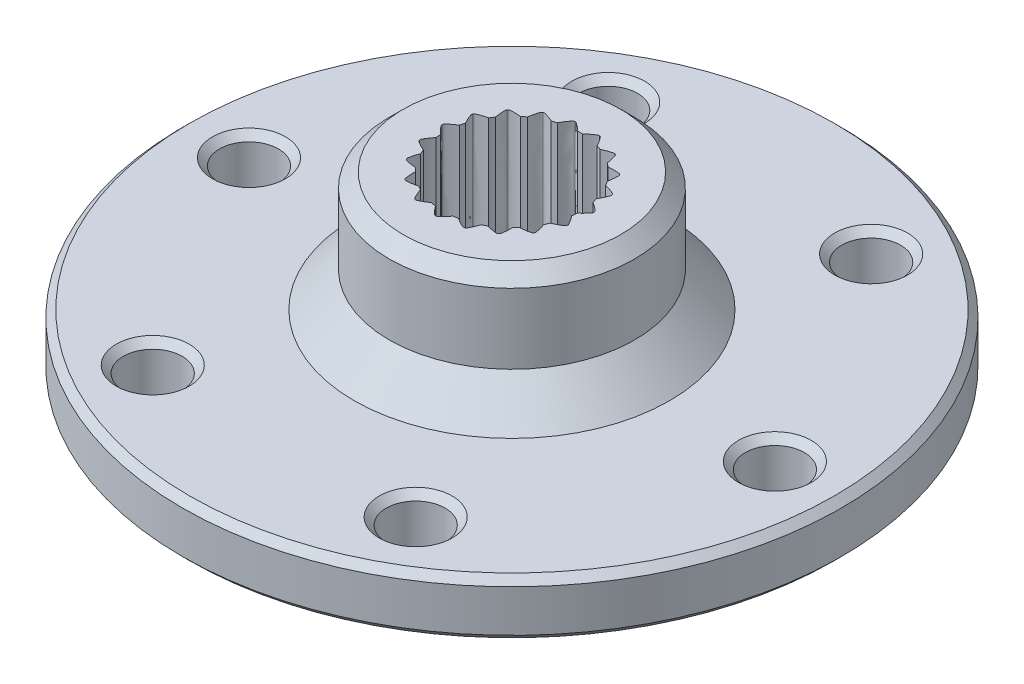
SolidWorks part; units mm, degrees
material "AISI 4340 Steel, normalized"
ref_plane "Front Plane" through (0, 0, 0) normal (0, 0, 1) x (1, 0, 0)
ref_plane "Top Plane" through (0, 0, 0) normal (0, 1, 0) x (1, 0, 0)
ref_plane "Right Plane" through (0, 0, 0) normal (1, 0, 0) x (0, 0, -1)
sketch "Sketch1" plane through (0, 0, 0) normal (0, 1, 0) x (1, 0, 0)
  circle A8 centre (0, 0) radius 47
  circle A9 centre (0, 0) radius 28
  circle A11 centre (-18.75, -32.476) radius 4.55
  circle A12 centre (18.75, -32.476) radius 4.55
  circle A13 centre (37.5, 0) radius 4.55
  circle A14 centre (18.75, 32.476) radius 4.55
  circle A15 centre (-18.75, 32.476) radius 4.55
  circle A16 centre (-37.5, 0) radius 4.55
  circle A17 centre (0, 0) radius 37.5 construction
  dimension "D1" = 94
  dimension "D2" = 56
  dimension "D3" = 9.1
  dimension "D5" = 75
  dimension "D4" = 18.75
extrude "Boss-Extrude1" add sketch "Sketch1" along normal blind 8 contours A9 | A8 A16 A15 A14 A13 A12 A11 A9 | A15 | A14 | A13 | A12 | A11 | A16 region at (-45.6706, 0, 0) region at (0, 0, 0) region at (-18.75, 0, 32.476) region at (18.75, 0, 32.476) region at (37.5, 0, 0) region at (18.75, 0, -32.476) region at (-18.75, 0, -32.476)
sketch "Sketch17" plane through (0, 8, 0) normal (0, 1, 0) x (1, 0, 0)
  circle A0 centre (-18.75, -32.476) radius 4.55
  circle A1 centre (18.75, -32.476) radius 4.55
  circle A2 centre (37.5, 0) radius 4.55
  circle A3 centre (18.75, 32.476) radius 4.55
  circle A4 centre (-18.75, 32.476) radius 4.55
  circle A5 centre (-37.5, 0) radius 4.55
  circle A6 centre (0, 0) radius 37.5 construction
  circle A7 centre (0, 0) radius 47 construction
  point P1 (-37.5, 0)
  point P2 (-18.75, -32.476)
  point P3 (18.75, -32.476)
  point P4 (37.5, 0)
  point P5 (18.75, 32.476)
  point P6 (-18.75, 32.476)
  dimension "D1" = 9.1
  dimension "D2" = 75
  dimension "D3" = 18.75
  dimension "D4" = 37.5
hole_wizard "M8 Clearance Hole1" positions "Sketch17" profile "Sketch18" hole size "M8" standard "DIN" end condition through all
sketch "Sketch18" plane through (-18.75, 8, -32.476) normal (1, 0, 0) x (0, 0, 1)
  line L0 (0, 0) -> (0, 8)
  line L1 (0, 8) -> (4.2, 8)
  line L2 (4.2, 8) -> (4.2, 0)
  line L5 (4.2, 0) -> (0, 0)
  line L11 (0, -6.35) -> (0, 107.95) construction
  dimension "Thru Hole Dia." = 8.4
  dimension "Thru Hole Depth" = 8
sketch "Sketch12" plane through (0, 8, 0) normal (0, 1, 0) x (1, 0, 0)
  circle A0 centre (0, 0) radius 17.5
  dimension "D1" = 35
extrude "Boss-Extrude5" add sketch "Sketch12" along normal blind 17 contours A0
sketch "Sketch13" plane through (0, 0, 0) normal (0, -1, 0) x (1, 0, 0)
  circle A0 centre (0, 0) radius 28
  dimension "D1" = 56
extrude "Boss-Extrude6" add sketch "Sketch13" along normal blind 5.08
sketch "Sketch16" plane through (0, 0, 0) normal (0, 1, 0) x (1, 0, 0)
  line B0 (1.8668, 11.187) -> (2.1421, 11.1376)
  line B1 (2.1421, 11.1376) -> (2.416, 11.0814)
  line B2 (2.416, 11.0814) -> (2.491, 11.1676)
  line B3 (2.491, 11.1676) -> (2.5708, 11.2556)
  line B4 (2.5708, 11.2556) -> (2.6534, 11.343)
  line B5 (2.6534, 11.343) -> (2.7388, 11.4297)
  line B6 (2.7388, 11.4297) -> (2.8266, 11.5155)
  line B7 (2.8266, 11.5155) -> (2.9189, 11.6021)
  line B8 (2.9189, 11.6021) -> (3.0133, 11.6874)
  line B9 (3.0133, 11.6874) -> (3.1122, 11.7733)
  line B10 (3.1122, 11.7733) -> (3.2129, 11.8575)
  line B11 (3.2129, 11.8575) -> (3.3178, 11.942)
  line B12 (3.3178, 11.942) -> (3.4243, 12.0245)
  line B13 (3.4243, 12.0245) -> (3.5292, 12.1028)
  line B14 (3.5292, 12.1028) -> (3.5601, 12.1214)
  line B15 (3.5601, 12.1214) -> (3.594, 12.1339)
  line B16 (3.594, 12.1339) -> (3.6296, 12.14)
  line B17 (3.6296, 12.14) -> (3.6657, 12.1394)
  line B18 (3.6657, 12.1394) -> (3.701, 12.1321)
  line B19 (3.701, 12.1321) -> (3.9104, 12.0662)
  line B20 (3.9104, 12.0662) -> (4.1185, 11.9968)
  line B21 (4.1185, 11.9968) -> (4.3254, 11.9237)
  line B22 (4.3254, 11.9237) -> (4.531, 11.8471)
  line B23 (4.531, 11.8471) -> (4.5634, 11.8312)
  line B24 (4.5634, 11.8312) -> (4.5923, 11.8095)
  line B25 (4.5923, 11.8095) -> (4.6167, 11.7829)
  line B26 (4.6167, 11.7829) -> (4.6357, 11.7522)
  line B27 (4.6357, 11.7522) -> (4.6487, 11.7185)
  line B28 (4.6487, 11.7185) -> (4.6833, 11.5923)
  line B29 (4.6833, 11.5923) -> (4.7167, 11.4617)
  line B30 (4.7167, 11.4617) -> (4.7476, 11.3306)
  line B31 (4.7476, 11.3306) -> (4.7754, 11.2023)
  line B32 (4.7754, 11.2023) -> (4.8006, 11.0738)
  line B33 (4.8006, 11.0738) -> (4.8228, 10.9485)
  line B34 (4.8228, 10.9485) -> (4.8424, 10.8235)
  line B35 (4.8424, 10.8235) -> (4.859, 10.7019)
  line B36 (4.859, 10.7019) -> (4.8731, 10.581)
  line B37 (4.8731, 10.581) -> (4.8846, 10.4612)
  line B38 (4.8846, 10.4612) -> (4.8935, 10.3428)
  line B39 (4.8935, 10.3428) -> (4.8997, 10.2287)
  line B40 (4.8997, 10.2287) -> (5.1505, 10.1048)
  line B41 (5.1505, 10.1048) -> (5.398, 9.9747)
  line B42 (5.398, 9.9747) -> (5.6424, 9.8386)
  line B43 (5.6424, 9.8386) -> (5.8832, 9.6965)
  line B44 (5.8832, 9.6965) -> (5.9822, 9.7537)
  line B45 (5.9822, 9.7537) -> (6.0861, 9.811)
  line B46 (6.0861, 9.811) -> (6.1927, 9.8669)
  line B47 (6.1927, 9.8669) -> (6.3016, 9.9212)
  line B48 (6.3016, 9.9212) -> (6.4125, 9.9737)
  line B49 (6.4125, 9.9737) -> (6.5279, 10.0257)
  line B50 (6.5279, 10.0257) -> (6.645, 10.0757)
  line B51 (6.645, 10.0757) -> (6.7663, 10.1248)
  line B52 (6.7663, 10.1248) -> (6.8889, 10.1718)
  line B53 (6.8889, 10.1718) -> (7.0156, 10.2176)
  line B54 (7.0156, 10.2176) -> (7.1431, 10.2611)
  line B55 (7.1431, 10.2611) -> (7.2677, 10.3012)
  line B56 (7.2677, 10.3012) -> (7.303, 10.3087)
  line B57 (7.303, 10.3087) -> (7.3391, 10.3095)
  line B58 (7.3391, 10.3095) -> (7.3748, 10.3037)
  line B59 (7.3748, 10.3037) -> (7.4087, 10.2914)
  line B60 (7.4087, 10.2914) -> (7.4398, 10.273)
  line B61 (7.4398, 10.273) -> (7.6164, 10.1428)
  line B62 (7.6164, 10.1428) -> (7.7907, 10.0095)
  line B63 (7.7907, 10.0095) -> (7.9627, 9.8732)
  line B64 (7.9627, 9.8732) -> (8.1323, 9.734)
  line B65 (8.1323, 9.734) -> (8.1577, 9.7084)
  line B66 (8.1577, 9.7084) -> (8.178, 9.6785)
  line B67 (8.178, 9.6785) -> (8.1924, 9.6454)
  line B68 (8.1924, 9.6454) -> (8.2004, 9.6102)
  line B69 (8.2004, 9.6102) -> (8.2018, 9.5741)
  line B70 (8.2018, 9.5741) -> (8.1936, 9.4435)
  line B71 (8.1936, 9.4435) -> (8.1827, 9.3092)
  line B72 (8.1827, 9.3092) -> (8.1694, 9.1751)
  line B73 (8.1694, 9.1751) -> (8.154, 9.0448)
  line B74 (8.154, 9.0448) -> (8.1362, 8.9151)
  line B75 (8.1362, 8.9151) -> (8.1164, 8.7894)
  line B76 (8.1164, 8.7894) -> (8.0944, 8.6647)
  line B77 (8.0944, 8.6647) -> (8.0706, 8.5443)
  line B78 (8.0706, 8.5443) -> (8.0447, 8.4254)
  line B79 (8.0447, 8.4254) -> (8.0167, 8.3084)
  line B80 (8.0167, 8.3084) -> (7.9867, 8.1935)
  line B81 (7.9867, 8.1935) -> (7.9555, 8.0835)
  line B82 (7.9555, 8.0835) -> (8.1524, 7.8849)
  line B83 (8.1524, 7.8849) -> (8.3443, 7.6815)
  line B84 (8.3443, 7.6815) -> (8.5312, 7.4734)
  line B85 (8.5312, 7.4734) -> (8.7129, 7.2608)
  line B86 (8.7129, 7.2608) -> (8.8251, 7.2828)
  line B87 (8.8251, 7.2828) -> (8.942, 7.3032)
  line B88 (8.942, 7.3032) -> (9.061, 7.3215)
  line B89 (9.061, 7.3215) -> (9.1816, 7.3375)
  line B90 (9.1816, 7.3375) -> (9.3035, 7.3512)
  line B91 (9.3035, 7.3512) -> (9.4296, 7.3629)
  line B92 (9.4296, 7.3629) -> (9.5565, 7.3722)
  line B93 (9.5565, 7.3722) -> (9.6872, 7.3792)
  line B94 (9.6872, 7.3792) -> (9.8184, 7.3838)
  line B95 (9.8184, 7.3838) -> (9.9531, 7.386)
  line B96 (9.9531, 7.386) -> (10.0879, 7.3858)
  line B97 (10.0879, 7.3858) -> (10.2187, 7.3832)
  line B98 (10.2187, 7.3832) -> (10.2546, 7.3788)
  line B99 (10.2546, 7.3788) -> (10.289, 7.3679)
  line B100 (10.289, 7.3679) -> (10.3208, 7.3508)
  line B101 (10.3208, 7.3508) -> (10.3489, 7.3282)
  line B102 (10.3489, 7.3282) -> (10.3723, 7.3007)
  line B103 (10.3723, 7.3007) -> (10.4971, 7.1202)
  line B104 (10.4971, 7.1202) -> (10.6187, 6.9375)
  line B105 (10.6187, 6.9375) -> (10.7371, 6.7528)
  line B106 (10.7371, 6.7528) -> (10.8523, 6.566)
  line B107 (10.8523, 6.566) -> (10.868, 6.5336)
  line B108 (10.868, 6.5336) -> (10.8775, 6.4987)
  line B109 (10.8775, 6.4987) -> (10.8804, 6.4627)
  line B110 (10.8804, 6.4627) -> (10.8765, 6.4268)
  line B111 (10.8765, 6.4268) -> (10.8661, 6.3922)
  line B112 (10.8661, 6.3922) -> (10.8159, 6.2714)
  line B113 (10.8159, 6.2714) -> (10.7621, 6.1479)
  line B114 (10.7621, 6.1479) -> (10.7059, 6.0254)
  line B115 (10.7059, 6.0254) -> (10.649, 5.9071)
  line B116 (10.649, 5.9071) -> (10.59, 5.7902)
  line B117 (10.59, 5.7902) -> (10.5305, 5.6777)
  line B118 (10.5305, 5.6777) -> (10.4692, 5.567)
  line B119 (10.4692, 5.567) -> (10.4077, 5.4608)
  line B120 (10.4077, 5.4608) -> (10.3446, 5.3568)
  line B121 (10.3446, 5.3568) -> (10.2801, 5.2552)
  line B122 (10.2801, 5.2552) -> (10.2144, 5.1563)
  line B123 (10.2144, 5.1563) -> (10.1492, 5.0624)
  line B124 (10.1492, 5.0624) -> (10.2709, 4.8106)
  line B125 (10.2709, 4.8106) -> (10.3864, 4.5559)
  line B126 (10.3864, 4.5559) -> (10.4956, 4.2984)
  line B127 (10.4956, 4.2984) -> (10.5984, 4.0383)
  line B128 (10.5984, 4.0383) -> (10.7116, 4.0227)
  line B129 (10.7116, 4.0227) -> (10.8289, 4.0041)
  line B130 (10.8289, 4.0041) -> (10.9473, 3.9827)
  line B131 (10.9473, 3.9827) -> (11.0666, 3.9587)
  line B132 (11.0666, 3.9587) -> (11.1864, 3.932)
  line B133 (11.1864, 3.932) -> (11.3094, 3.9022)
  line B134 (11.3094, 3.9022) -> (11.4324, 3.8697)
  line B135 (11.4324, 3.8697) -> (11.5584, 3.834)
  line B136 (11.5584, 3.834) -> (11.684, 3.7957)
  line B137 (11.684, 3.7957) -> (11.8121, 3.7541)
  line B138 (11.8121, 3.7541) -> (11.9394, 3.7101)
  line B139 (11.9394, 3.7101) -> (12.0624, 3.6651)
  line B140 (12.0624, 3.6651) -> (12.0948, 3.6494)
  line B141 (12.0948, 3.6494) -> (12.1238, 3.6279)
  line B142 (12.1238, 3.6279) -> (12.1484, 3.6014)
  line B143 (12.1484, 3.6014) -> (12.1676, 3.5708)
  line B144 (12.1676, 3.5708) -> (12.1808, 3.5372)
  line B145 (12.1808, 3.5372) -> (12.2402, 3.326)
  line B146 (12.2402, 3.326) -> (12.2959, 3.1137)
  line B147 (12.2959, 3.1137) -> (12.3479, 2.9006)
  line B148 (12.3479, 2.9006) -> (12.3963, 2.6865)
  line B149 (12.3963, 2.6865) -> (12.4006, 2.6507)
  line B150 (12.4006, 2.6507) -> (12.3983, 2.6147)
  line B151 (12.3983, 2.6147) -> (12.3893, 2.5797)
  line B152 (12.3893, 2.5797) -> (12.374, 2.547)
  line B153 (12.374, 2.547) -> (12.3529, 2.5177)
  line B154 (12.3529, 2.5177) -> (12.2662, 2.4196)
  line B155 (12.2662, 2.4196) -> (12.1752, 2.3203)
  line B156 (12.1752, 2.3203) -> (12.0823, 2.2227)
  line B157 (12.0823, 2.2227) -> (11.9901, 2.1293)
  line B158 (11.9901, 2.1293) -> (11.8963, 2.0379)
  line B159 (11.8963, 2.0379) -> (11.8035, 1.9508)
  line B160 (11.8035, 1.9508) -> (11.7096, 1.866)
  line B161 (11.7096, 1.866) -> (11.6169, 1.7856)
  line B162 (11.6169, 1.7856) -> (11.5234, 1.7077)
  line B163 (11.5234, 1.7077) -> (11.4294, 1.6325)
  line B164 (11.4294, 1.6325) -> (11.3352, 1.5603)
  line B165 (11.3352, 1.5603) -> (11.243, 1.4927)
  line B166 (11.243, 1.4927) -> (11.2764, 1.215)
  line B167 (11.2764, 1.215) -> (11.3029, 0.9366)
  line B168 (11.3029, 0.9366) -> (11.3226, 0.6576)
  line B169 (11.3226, 0.6576) -> (11.3354, 0.3782)
  line B170 (11.3354, 0.3782) -> (11.4374, 0.3267)
  line B171 (11.4374, 0.3267) -> (11.5422, 0.271)
  line B172 (11.5422, 0.271) -> (11.6473, 0.2123)
  line B173 (11.6473, 0.2123) -> (11.7523, 0.1509)
  line B174 (11.7523, 0.1509) -> (11.857, 0.0868)
  line B175 (11.857, 0.0868) -> (11.9636, 0.0186)
  line B176 (11.9636, 0.0186) -> (12.0695, -0.0521)
  line B177 (12.0695, -0.0521) -> (12.177, -0.1268)
  line B178 (12.177, -0.1268) -> (12.2834, -0.2037)
  line B179 (12.2834, -0.2037) -> (12.391, -0.2847)
  line B180 (12.391, -0.2847) -> (12.4972, -0.3677)
  line B181 (12.4972, -0.3677) -> (12.5988, -0.4501)
  line B182 (12.5988, -0.4501) -> (12.6245, -0.4756)
  line B183 (12.6245, -0.4756) -> (12.6449, -0.5053)
  line B184 (12.6449, -0.5053) -> (12.6595, -0.5383)
  line B185 (12.6595, -0.5383) -> (12.6678, -0.5735)
  line B186 (12.6678, -0.5735) -> (12.6694, -0.6096)
  line B187 (12.6694, -0.6096) -> (12.6569, -0.8286)
  line B188 (12.6569, -0.8286) -> (12.6407, -1.0474)
  line B189 (12.6407, -1.0474) -> (12.6207, -1.2659)
  line B190 (12.6207, -1.2659) -> (12.5969, -1.4841)
  line B191 (12.5969, -1.4841) -> (12.5894, -1.5194)
  line B192 (12.5894, -1.5194) -> (12.5755, -1.5527)
  line B193 (12.5755, -1.5527) -> (12.5556, -1.5829)
  line B194 (12.5556, -1.5829) -> (12.5305, -1.6088)
  line B195 (12.5305, -1.6088) -> (12.5011, -1.6297)
  line B196 (12.5011, -1.6297) -> (12.3872, -1.6943)
  line B197 (12.3872, -1.6943) -> (12.2689, -1.7587)
  line B198 (12.2689, -1.7587) -> (12.1494, -1.8208)
  line B199 (12.1494, -1.8208) -> (12.0318, -1.8792)
  line B200 (12.0318, -1.8792) -> (11.9135, -1.9352)
  line B201 (11.9135, -1.9352) -> (11.7974, -1.9875)
  line B202 (11.7974, -1.9875) -> (11.681, -2.0372)
  line B203 (11.681, -2.0372) -> (11.5672, -2.0832)
  line B204 (11.5672, -2.0832) -> (11.4535, -2.1265)
  line B205 (11.4535, -2.1265) -> (11.3402, -2.1671)
  line B206 (11.3402, -2.1671) -> (11.2277, -2.2048)
  line B207 (11.2277, -2.2048) -> (11.1185, -2.2388)
  line B208 (11.1185, -2.2388) -> (11.0599, -2.5123)
  line B209 (11.0599, -2.5123) -> (10.9946, -2.7842)
  line B210 (10.9946, -2.7842) -> (10.9226, -3.0545)
  line B211 (10.9226, -3.0545) -> (10.844, -3.3229)
  line B212 (10.844, -3.3229) -> (10.9238, -3.4047)
  line B213 (10.9238, -3.4047) -> (11.0048, -3.4915)
  line B214 (11.0048, -3.4915) -> (11.0852, -3.5811)
  line B215 (11.0852, -3.5811) -> (11.1645, -3.6733)
  line B216 (11.1645, -3.6733) -> (11.2427, -3.7679)
  line B217 (11.2427, -3.7679) -> (11.3214, -3.867)
  line B218 (11.3214, -3.867) -> (11.3986, -3.9682)
  line B219 (11.3986, -3.9682) -> (11.4761, -4.0738)
  line B220 (11.4761, -4.0738) -> (11.5517, -4.1811)
  line B221 (11.5517, -4.1811) -> (11.6272, -4.2927)
  line B222 (11.6272, -4.2927) -> (11.7007, -4.4056)
  line B223 (11.7007, -4.4056) -> (11.7701, -4.5165)
  line B224 (11.7701, -4.5165) -> (11.786, -4.5489)
  line B225 (11.786, -4.5489) -> (11.7957, -4.5837)
  line B226 (11.7957, -4.5837) -> (11.7988, -4.6197)
  line B227 (11.7988, -4.6197) -> (11.7952, -4.6556)
  line B228 (11.7952, -4.6556) -> (11.785, -4.6903)
  line B229 (11.785, -4.6903) -> (11.7021, -4.8934)
  line B230 (11.7021, -4.8934) -> (11.6157, -5.0951)
  line B231 (11.6157, -5.0951) -> (11.5258, -5.2953)
  line B232 (11.5258, -5.2953) -> (11.4325, -5.4939)
  line B233 (11.4325, -5.4939) -> (11.4139, -5.5248)
  line B234 (11.4139, -5.5248) -> (11.3899, -5.5518)
  line B235 (11.3899, -5.5518) -> (11.3614, -5.5739)
  line B236 (11.3614, -5.5739) -> (11.3292, -5.5903)
  line B237 (11.3292, -5.5903) -> (11.2946, -5.6005)
  line B238 (11.2946, -5.6005) -> (11.1659, -5.6246)
  line B239 (11.1659, -5.6246) -> (11.0331, -5.6471)
  line B240 (11.0331, -5.6471) -> (10.8998, -5.6671)
  line B241 (10.8998, -5.6671) -> (10.7697, -5.6841)
  line B242 (10.7697, -5.6841) -> (10.6396, -5.6987)
  line B243 (10.6396, -5.6987) -> (10.5129, -5.7104)
  line B244 (10.5129, -5.7104) -> (10.3866, -5.7196)
  line B245 (10.3866, -5.7196) -> (10.2641, -5.7262)
  line B246 (10.2641, -5.7262) -> (10.1425, -5.7302)
  line B247 (10.1425, -5.7302) -> (10.0221, -5.7318)
  line B248 (10.0221, -5.7318) -> (9.9034, -5.7309)
  line B249 (9.9034, -5.7309) -> (9.7892, -5.7277)
  line B250 (9.7892, -5.7277) -> (9.6449, -5.9673)
  line B251 (9.6449, -5.9673) -> (9.4949, -6.2033)
  line B252 (9.4949, -6.2033) -> (9.339, -6.4355)
  line B253 (9.339, -6.4355) -> (9.1775, -6.6639)
  line B254 (9.1775, -6.6639) -> (9.2264, -6.7672)
  line B255 (9.2264, -6.7672) -> (9.2749, -6.8755)
  line B256 (9.2749, -6.8755) -> (9.3218, -6.9864)
  line B257 (9.3218, -6.9864) -> (9.3669, -7.0994)
  line B258 (9.3669, -7.0994) -> (9.4101, -7.2142)
  line B259 (9.4101, -7.2142) -> (9.4524, -7.3336)
  line B260 (9.4524, -7.3336) -> (9.4926, -7.4543)
  line B261 (9.4926, -7.4543) -> (9.5315, -7.5793)
  line B262 (9.5315, -7.5793) -> (9.5682, -7.7054)
  line B263 (9.5682, -7.7054) -> (9.6034, -7.8354)
  line B264 (9.6034, -7.8354) -> (9.6362, -7.9661)
  line B265 (9.6362, -7.9661) -> (9.6658, -8.0936)
  line B266 (9.6658, -8.0936) -> (9.6704, -8.1294)
  line B267 (9.6704, -8.1294) -> (9.6682, -8.1654)
  line B268 (9.6682, -8.1654) -> (9.6595, -8.2005)
  line B269 (9.6595, -8.2005) -> (9.6444, -8.2333)
  line B270 (9.6444, -8.2333) -> (9.6235, -8.2627)
  line B271 (9.6235, -8.2627) -> (9.4792, -8.428)
  line B272 (9.4792, -8.428) -> (9.332, -8.5907)
  line B273 (9.332, -8.5907) -> (9.182, -8.7508)
  line B274 (9.182, -8.7508) -> (9.0292, -8.9083)
  line B275 (9.0292, -8.9083) -> (9.0016, -8.9316)
  line B276 (9.0016, -8.9316) -> (8.9701, -8.9493)
  line B277 (8.9701, -8.9493) -> (8.9359, -8.9609)
  line B278 (8.9359, -8.9609) -> (8.9002, -8.966)
  line B279 (8.9002, -8.966) -> (8.8641, -8.9644)
  line B280 (8.8641, -8.9644) -> (8.7346, -8.9454)
  line B281 (8.7346, -8.9454) -> (8.6017, -8.9235)
  line B282 (8.6017, -8.9235) -> (8.4692, -8.8992)
  line B283 (8.4692, -8.8992) -> (8.3405, -8.8731)
  line B284 (8.3405, -8.8731) -> (8.2127, -8.8446)
  line B285 (8.2127, -8.8446) -> (8.0891, -8.8145)
  line B286 (8.0891, -8.8145) -> (7.9667, -8.7822)
  line B287 (7.9667, -8.7822) -> (7.8486, -8.7486)
  line B288 (7.8486, -8.7486) -> (7.7323, -8.713)
  line B289 (7.7323, -8.713) -> (7.618, -8.6754)
  line B290 (7.618, -8.6754) -> (7.506, -8.6361)
  line B291 (7.506, -8.6361) -> (7.399, -8.5959)
  line B292 (7.399, -8.5959) -> (7.1848, -8.7757)
  line B293 (7.1848, -8.7757) -> (6.9662, -8.9502)
  line B294 (6.9662, -8.9502) -> (6.7434, -9.1192)
  line B295 (6.7434, -9.1192) -> (6.5165, -9.2827)
  line B296 (6.5165, -9.2827) -> (6.5292, -9.3963)
  line B297 (6.5292, -9.3963) -> (6.5399, -9.5146)
  line B298 (6.5399, -9.5146) -> (6.5482, -9.6346)
  line B299 (6.5482, -9.6346) -> (6.5542, -9.7561)
  line B300 (6.5542, -9.7561) -> (6.5578, -9.8788)
  line B301 (6.5578, -9.8788) -> (6.559, -10.0054)
  line B302 (6.559, -10.0054) -> (6.5578, -10.1327)
  line B303 (6.5578, -10.1327) -> (6.5541, -10.2635)
  line B304 (6.5541, -10.2635) -> (6.5478, -10.3946)
  line B305 (6.5478, -10.3946) -> (6.5389, -10.5291)
  line B306 (6.5389, -10.5291) -> (6.5275, -10.6633)
  line B307 (6.5275, -10.6633) -> (6.5141, -10.7935)
  line B308 (6.5141, -10.7935) -> (6.5068, -10.8289)
  line B309 (6.5068, -10.8289) -> (6.4931, -10.8623)
  line B310 (6.4931, -10.8623) -> (6.4734, -10.8926)
  line B311 (6.4734, -10.8926) -> (6.4485, -10.9187)
  line B312 (6.4485, -10.9187) -> (6.4192, -10.9398)
  line B313 (6.4192, -10.9398) -> (6.229, -11.0492)
  line B314 (6.229, -11.0492) -> (6.0369, -11.1553)
  line B315 (6.0369, -11.1553) -> (5.8431, -11.258)
  line B316 (5.8431, -11.258) -> (5.6474, -11.3574)
  line B317 (5.6474, -11.3574) -> (5.6138, -11.3704)
  line B318 (5.6138, -11.3704) -> (5.5783, -11.377)
  line B319 (5.5783, -11.377) -> (5.5421, -11.3769)
  line B320 (5.5421, -11.3769) -> (5.5067, -11.3701)
  line B321 (5.5067, -11.3701) -> (5.4731, -11.3569)
  line B322 (5.4731, -11.3569) -> (5.3568, -11.2969)
  line B323 (5.3568, -11.2969) -> (5.2382, -11.233)
  line B324 (5.2382, -11.233) -> (5.1207, -11.1669)
  line B325 (5.1207, -11.1669) -> (5.0075, -11.1005)
  line B326 (5.0075, -11.1005) -> (4.8959, -11.032)
  line B327 (4.8959, -11.032) -> (4.7887, -10.9634)
  line B328 (4.7887, -10.9634) -> (4.6834, -10.8932)
  line B329 (4.6834, -10.8932) -> (4.5827, -10.8231)
  line B330 (4.5827, -10.8231) -> (4.4842, -10.7516)
  line B331 (4.4842, -10.7516) -> (4.3883, -10.6789)
  line B332 (4.3883, -10.6789) -> (4.2952, -10.6053)
  line B333 (4.2952, -10.6053) -> (4.207, -10.5326)
  line B334 (4.207, -10.5326) -> (3.946, -10.6331)
  line B335 (3.946, -10.6331) -> (3.6826, -10.7272)
  line B336 (3.6826, -10.7272) -> (3.417, -10.8147)
  line B337 (3.417, -10.8147) -> (3.1493, -10.8957)
  line B338 (3.1493, -10.8957) -> (3.1244, -11.0072)
  line B339 (3.1244, -11.0072) -> (3.0962, -11.1225)
  line B340 (3.0962, -11.1225) -> (3.0651, -11.2388)
  line B341 (3.0651, -11.2388) -> (3.0313, -11.3557)
  line B342 (3.0313, -11.3557) -> (2.9948, -11.4729)
  line B343 (2.9948, -11.4729) -> (2.9549, -11.593)
  line B344 (2.9549, -11.593) -> (2.9124, -11.713)
  line B345 (2.9124, -11.713) -> (2.8664, -11.8355)
  line B346 (2.8664, -11.8355) -> (2.8179, -11.9575)
  line B347 (2.8179, -11.9575) -> (2.7658, -12.0818)
  line B348 (2.7658, -12.0818) -> (2.7114, -12.205)
  line B349 (2.7114, -12.205) -> (2.6565, -12.3238)
  line B350 (2.6565, -12.3238) -> (2.6381, -12.3549)
  line B351 (2.6381, -12.3549) -> (2.6143, -12.382)
  line B352 (2.6143, -12.382) -> (2.5859, -12.4043)
  line B353 (2.5859, -12.4043) -> (2.5538, -12.4209)
  line B354 (2.5538, -12.4209) -> (2.5193, -12.4313)
  line B355 (2.5193, -12.4313) -> (2.3038, -12.4731)
  line B356 (2.3038, -12.4731) -> (2.0877, -12.5111)
  line B357 (2.0877, -12.5111) -> (1.871, -12.5453)
  line B358 (1.871, -12.5453) -> (1.6537, -12.5758)
  line B359 (1.6537, -12.5758) -> (1.6176, -12.5771)
  line B360 (1.6176, -12.5771) -> (1.5819, -12.5718)
  line B361 (1.5819, -12.5718) -> (1.5478, -12.56)
  line B362 (1.5478, -12.56) -> (1.5165, -12.5421)
  line B363 (1.5165, -12.5421) -> (1.489, -12.5186)
  line B364 (1.489, -12.5186) -> (1.3984, -12.4241)
  line B365 (1.3984, -12.4241) -> (1.307, -12.3252)
  line B366 (1.307, -12.3252) -> (1.2174, -12.2246)
  line B367 (1.2174, -12.2246) -> (1.1319, -12.125)
  line B368 (1.1319, -12.125) -> (1.0486, -12.024)
  line B369 (1.0486, -12.024) -> (0.9694, -11.9243)
  line B370 (0.9694, -11.9243) -> (0.8927, -11.8237)
  line B371 (0.8927, -11.8237) -> (0.8202, -11.7246)
  line B372 (0.8202, -11.7246) -> (0.7502, -11.6251)
  line B373 (0.7502, -11.6251) -> (0.6831, -11.5252)
  line B374 (0.6831, -11.5252) -> (0.6189, -11.4253)
  line B375 (0.6189, -11.4253) -> (0.5591, -11.3279)
  line B376 (0.5591, -11.3279) -> (0.2797, -11.3382)
  line B377 (0.2797, -11.3382) -> (0, -11.3417)
  line B378 (0, -11.3417) -> (-0.2797, -11.3382)
  line B379 (-0.2797, -11.3382) -> (-0.5591, -11.3279)
  line B380 (-0.5591, -11.3279) -> (-0.6189, -11.4253)
  line B381 (-0.6189, -11.4253) -> (-0.6831, -11.5252)
  line B382 (-0.6831, -11.5252) -> (-0.7502, -11.6251)
  line B383 (-0.7502, -11.6251) -> (-0.8202, -11.7246)
  line B384 (-0.8202, -11.7246) -> (-0.8927, -11.8237)
  line B385 (-0.8927, -11.8237) -> (-0.9694, -11.9243)
  line B386 (-0.9694, -11.9243) -> (-1.0486, -12.024)
  line B387 (-1.0486, -12.024) -> (-1.1319, -12.125)
  line B388 (-1.1319, -12.125) -> (-1.2174, -12.2246)
  line B389 (-1.2174, -12.2246) -> (-1.307, -12.3252)
  line B390 (-1.307, -12.3252) -> (-1.3984, -12.4241)
  line B391 (-1.3984, -12.4241) -> (-1.489, -12.5186)
  line B392 (-1.489, -12.5186) -> (-1.5165, -12.5421)
  line B393 (-1.5165, -12.5421) -> (-1.5478, -12.56)
  line B394 (-1.5478, -12.56) -> (-1.5819, -12.5718)
  line B395 (-1.5819, -12.5718) -> (-1.6176, -12.5771)
  line B396 (-1.6176, -12.5771) -> (-1.6537, -12.5758)
  line B397 (-1.6537, -12.5758) -> (-1.871, -12.5453)
  line B398 (-1.871, -12.5453) -> (-2.0877, -12.5111)
  line B399 (-2.0877, -12.5111) -> (-2.3038, -12.4731)
  line B400 (-2.3038, -12.4731) -> (-2.5193, -12.4313)
  line B401 (-2.5193, -12.4313) -> (-2.5538, -12.4209)
  line B402 (-2.5538, -12.4209) -> (-2.5859, -12.4043)
  line B403 (-2.5859, -12.4043) -> (-2.6143, -12.382)
  line B404 (-2.6143, -12.382) -> (-2.6381, -12.3549)
  line B405 (-2.6381, -12.3549) -> (-2.6565, -12.3238)
  line B406 (-2.6565, -12.3238) -> (-2.7114, -12.205)
  line B407 (-2.7114, -12.205) -> (-2.7658, -12.0818)
  line B408 (-2.7658, -12.0818) -> (-2.8179, -11.9575)
  line B409 (-2.8179, -11.9575) -> (-2.8664, -11.8355)
  line B410 (-2.8664, -11.8355) -> (-2.9124, -11.713)
  line B411 (-2.9124, -11.713) -> (-2.9549, -11.593)
  line B412 (-2.9549, -11.593) -> (-2.9948, -11.4729)
  line B413 (-2.9948, -11.4729) -> (-3.0313, -11.3557)
  line B414 (-3.0313, -11.3557) -> (-3.0651, -11.2388)
  line B415 (-3.0651, -11.2388) -> (-3.0962, -11.1225)
  line B416 (-3.0962, -11.1225) -> (-3.1244, -11.0072)
  line B417 (-3.1244, -11.0072) -> (-3.1493, -10.8957)
  line B418 (-3.1493, -10.8957) -> (-3.417, -10.8147)
  line B419 (-3.417, -10.8147) -> (-3.6826, -10.7272)
  line B420 (-3.6826, -10.7272) -> (-3.946, -10.6331)
  line B421 (-3.946, -10.6331) -> (-4.207, -10.5326)
  line B422 (-4.207, -10.5326) -> (-4.2952, -10.6053)
  line B423 (-4.2952, -10.6053) -> (-4.3883, -10.6789)
  line B424 (-4.3883, -10.6789) -> (-4.4842, -10.7516)
  line B425 (-4.4842, -10.7516) -> (-4.5827, -10.8231)
  line B426 (-4.5827, -10.8231) -> (-4.6834, -10.8932)
  line B427 (-4.6834, -10.8932) -> (-4.7887, -10.9634)
  line B428 (-4.7887, -10.9634) -> (-4.8959, -11.032)
  line B429 (-4.8959, -11.032) -> (-5.0075, -11.1005)
  line B430 (-5.0075, -11.1005) -> (-5.1207, -11.1669)
  line B431 (-5.1207, -11.1669) -> (-5.2382, -11.233)
  line B432 (-5.2382, -11.233) -> (-5.3568, -11.2969)
  line B433 (-5.3568, -11.2969) -> (-5.4731, -11.3569)
  line B434 (-5.4731, -11.3569) -> (-5.5067, -11.3701)
  line B435 (-5.5067, -11.3701) -> (-5.5421, -11.3769)
  line B436 (-5.5421, -11.3769) -> (-5.5783, -11.377)
  line B437 (-5.5783, -11.377) -> (-5.6138, -11.3704)
  line B438 (-5.6138, -11.3704) -> (-5.6474, -11.3574)
  line B439 (-5.6474, -11.3574) -> (-5.8431, -11.258)
  line B440 (-5.8431, -11.258) -> (-6.0369, -11.1553)
  line B441 (-6.0369, -11.1553) -> (-6.229, -11.0492)
  line B442 (-6.229, -11.0492) -> (-6.4192, -10.9398)
  line B443 (-6.4192, -10.9398) -> (-6.4485, -10.9187)
  line B444 (-6.4485, -10.9187) -> (-6.4734, -10.8926)
  line B445 (-6.4734, -10.8926) -> (-6.4931, -10.8623)
  line B446 (-6.4931, -10.8623) -> (-6.5068, -10.8289)
  line B447 (-6.5068, -10.8289) -> (-6.5141, -10.7935)
  line B448 (-6.5141, -10.7935) -> (-6.5275, -10.6633)
  line B449 (-6.5275, -10.6633) -> (-6.5389, -10.5291)
  line B450 (-6.5389, -10.5291) -> (-6.5478, -10.3946)
  line B451 (-6.5478, -10.3946) -> (-6.5541, -10.2635)
  line B452 (-6.5541, -10.2635) -> (-6.5578, -10.1327)
  line B453 (-6.5578, -10.1327) -> (-6.559, -10.0054)
  line B454 (-6.559, -10.0054) -> (-6.5578, -9.8788)
  line B455 (-6.5578, -9.8788) -> (-6.5542, -9.7561)
  line B456 (-6.5542, -9.7561) -> (-6.5482, -9.6346)
  line B457 (-6.5482, -9.6346) -> (-6.5399, -9.5146)
  line B458 (-6.5399, -9.5146) -> (-6.5292, -9.3963)
  line B459 (-6.5292, -9.3963) -> (-6.5165, -9.2827)
  line B460 (-6.5165, -9.2827) -> (-6.7434, -9.1192)
  line B461 (-6.7434, -9.1192) -> (-6.9662, -8.9502)
  line B462 (-6.9662, -8.9502) -> (-7.1848, -8.7757)
  line B463 (-7.1848, -8.7757) -> (-7.399, -8.5959)
  line B464 (-7.399, -8.5959) -> (-7.506, -8.6361)
  line B465 (-7.506, -8.6361) -> (-7.618, -8.6754)
  line B466 (-7.618, -8.6754) -> (-7.7323, -8.713)
  line B467 (-7.7323, -8.713) -> (-7.8486, -8.7486)
  line B468 (-7.8486, -8.7486) -> (-7.9667, -8.7822)
  line B469 (-7.9667, -8.7822) -> (-8.0891, -8.8145)
  line B470 (-8.0891, -8.8145) -> (-8.2127, -8.8446)
  line B471 (-8.2127, -8.8446) -> (-8.3405, -8.8731)
  line B472 (-8.3405, -8.8731) -> (-8.4692, -8.8992)
  line B473 (-8.4692, -8.8992) -> (-8.6017, -8.9235)
  line B474 (-8.6017, -8.9235) -> (-8.7346, -8.9454)
  line B475 (-8.7346, -8.9454) -> (-8.8641, -8.9644)
  line B476 (-8.8641, -8.9644) -> (-8.9002, -8.966)
  line B477 (-8.9002, -8.966) -> (-8.9359, -8.9609)
  line B478 (-8.9359, -8.9609) -> (-8.9701, -8.9493)
  line B479 (-8.9701, -8.9493) -> (-9.0016, -8.9316)
  line B480 (-9.0016, -8.9316) -> (-9.0292, -8.9083)
  line B481 (-9.0292, -8.9083) -> (-9.182, -8.7508)
  line B482 (-9.182, -8.7508) -> (-9.332, -8.5907)
  line B483 (-9.332, -8.5907) -> (-9.4792, -8.428)
  line B484 (-9.4792, -8.428) -> (-9.6235, -8.2627)
  line B485 (-9.6235, -8.2627) -> (-9.6444, -8.2333)
  line B486 (-9.6444, -8.2333) -> (-9.6595, -8.2005)
  line B487 (-9.6595, -8.2005) -> (-9.6682, -8.1654)
  line B488 (-9.6682, -8.1654) -> (-9.6704, -8.1294)
  line B489 (-9.6704, -8.1294) -> (-9.6658, -8.0936)
  line B490 (-9.6658, -8.0936) -> (-9.6362, -7.9661)
  line B491 (-9.6362, -7.9661) -> (-9.6034, -7.8354)
  line B492 (-9.6034, -7.8354) -> (-9.5682, -7.7054)
  line B493 (-9.5682, -7.7054) -> (-9.5315, -7.5793)
  line B494 (-9.5315, -7.5793) -> (-9.4926, -7.4543)
  line B495 (-9.4926, -7.4543) -> (-9.4524, -7.3336)
  line B496 (-9.4524, -7.3336) -> (-9.4101, -7.2142)
  line B497 (-9.4101, -7.2142) -> (-9.3669, -7.0994)
  line B498 (-9.3669, -7.0994) -> (-9.3218, -6.9864)
  line B499 (-9.3218, -6.9864) -> (-9.2749, -6.8755)
  line B500 (-9.2749, -6.8755) -> (-9.2264, -6.7672)
  line B501 (-9.2264, -6.7672) -> (-9.1775, -6.6639)
  line B502 (-9.1775, -6.6639) -> (-9.339, -6.4355)
  line B503 (-9.339, -6.4355) -> (-9.4949, -6.2033)
  line B504 (-9.4949, -6.2033) -> (-9.6449, -5.9673)
  line B505 (-9.6449, -5.9673) -> (-9.7892, -5.7277)
  line B506 (-9.7892, -5.7277) -> (-9.9034, -5.7309)
  line B507 (-9.9034, -5.7309) -> (-10.0221, -5.7318)
  line B508 (-10.0221, -5.7318) -> (-10.1425, -5.7302)
  line B509 (-10.1425, -5.7302) -> (-10.2641, -5.7262)
  line B510 (-10.2641, -5.7262) -> (-10.3866, -5.7196)
  line B511 (-10.3866, -5.7196) -> (-10.5129, -5.7104)
  line B512 (-10.5129, -5.7104) -> (-10.6396, -5.6987)
  line B513 (-10.6396, -5.6987) -> (-10.7697, -5.6841)
  line B514 (-10.7697, -5.6841) -> (-10.8998, -5.6671)
  line B515 (-10.8998, -5.6671) -> (-11.0331, -5.6471)
  line B516 (-11.0331, -5.6471) -> (-11.1659, -5.6246)
  line B517 (-11.1659, -5.6246) -> (-11.2946, -5.6005)
  line B518 (-11.2946, -5.6005) -> (-11.3292, -5.5903)
  line B519 (-11.3292, -5.5903) -> (-11.3614, -5.5739)
  line B520 (-11.3614, -5.5739) -> (-11.3899, -5.5518)
  line B521 (-11.3899, -5.5518) -> (-11.4139, -5.5248)
  line B522 (-11.4139, -5.5248) -> (-11.4325, -5.4939)
  line B523 (-11.4325, -5.4939) -> (-11.5258, -5.2953)
  line B524 (-11.5258, -5.2953) -> (-11.6157, -5.0951)
  line B525 (-11.6157, -5.0951) -> (-11.7021, -4.8934)
  line B526 (-11.7021, -4.8934) -> (-11.785, -4.6903)
  line B527 (-11.785, -4.6903) -> (-11.7952, -4.6556)
  line B528 (-11.7952, -4.6556) -> (-11.7988, -4.6197)
  line B529 (-11.7988, -4.6197) -> (-11.7957, -4.5837)
  line B530 (-11.7957, -4.5837) -> (-11.786, -4.5489)
  line B531 (-11.786, -4.5489) -> (-11.7701, -4.5165)
  line B532 (-11.7701, -4.5165) -> (-11.7007, -4.4056)
  line B533 (-11.7007, -4.4056) -> (-11.6272, -4.2927)
  line B534 (-11.6272, -4.2927) -> (-11.5517, -4.1811)
  line B535 (-11.5517, -4.1811) -> (-11.4761, -4.0738)
  line B536 (-11.4761, -4.0738) -> (-11.3986, -3.9682)
  line B537 (-11.3986, -3.9682) -> (-11.3214, -3.867)
  line B538 (-11.3214, -3.867) -> (-11.2427, -3.7679)
  line B539 (-11.2427, -3.7679) -> (-11.1645, -3.6733)
  line B540 (-11.1645, -3.6733) -> (-11.0852, -3.5811)
  line B541 (-11.0852, -3.5811) -> (-11.0048, -3.4915)
  line B542 (-11.0048, -3.4915) -> (-10.9238, -3.4047)
  line B543 (-10.9238, -3.4047) -> (-10.844, -3.3229)
  line B544 (-10.844, -3.3229) -> (-10.9226, -3.0545)
  line B545 (-10.9226, -3.0545) -> (-10.9946, -2.7842)
  line B546 (-10.9946, -2.7842) -> (-11.0599, -2.5123)
  line B547 (-11.0599, -2.5123) -> (-11.1185, -2.2388)
  line B548 (-11.1185, -2.2388) -> (-11.2277, -2.2048)
  line B549 (-11.2277, -2.2048) -> (-11.3402, -2.1671)
  line B550 (-11.3402, -2.1671) -> (-11.4535, -2.1265)
  line B551 (-11.4535, -2.1265) -> (-11.5672, -2.0832)
  line B552 (-11.5672, -2.0832) -> (-11.681, -2.0372)
  line B553 (-11.681, -2.0372) -> (-11.7974, -1.9875)
  line B554 (-11.7974, -1.9875) -> (-11.9135, -1.9352)
  line B555 (-11.9135, -1.9352) -> (-12.0318, -1.8792)
  line B556 (-12.0318, -1.8792) -> (-12.1494, -1.8208)
  line B557 (-12.1494, -1.8208) -> (-12.2689, -1.7587)
  line B558 (-12.2689, -1.7587) -> (-12.3872, -1.6943)
  line B559 (-12.3872, -1.6943) -> (-12.5011, -1.6297)
  line B560 (-12.5011, -1.6297) -> (-12.5305, -1.6088)
  line B561 (-12.5305, -1.6088) -> (-12.5556, -1.5829)
  line B562 (-12.5556, -1.5829) -> (-12.5755, -1.5527)
  line B563 (-12.5755, -1.5527) -> (-12.5894, -1.5194)
  line B564 (-12.5894, -1.5194) -> (-12.5969, -1.4841)
  line B565 (-12.5969, -1.4841) -> (-12.6207, -1.2659)
  line B566 (-12.6207, -1.2659) -> (-12.6407, -1.0474)
  line B567 (-12.6407, -1.0474) -> (-12.6569, -0.8286)
  line B568 (-12.6569, -0.8286) -> (-12.6694, -0.6096)
  line B569 (-12.6694, -0.6096) -> (-12.6678, -0.5735)
  line B570 (-12.6678, -0.5735) -> (-12.6595, -0.5383)
  line B571 (-12.6595, -0.5383) -> (-12.6449, -0.5053)
  line B572 (-12.6449, -0.5053) -> (-12.6245, -0.4756)
  line B573 (-12.6245, -0.4756) -> (-12.5988, -0.4501)
  line B574 (-12.5988, -0.4501) -> (-12.4972, -0.3677)
  line B575 (-12.4972, -0.3677) -> (-12.391, -0.2847)
  line B576 (-12.391, -0.2847) -> (-12.2834, -0.2037)
  line B577 (-12.2834, -0.2037) -> (-12.177, -0.1268)
  line B578 (-12.177, -0.1268) -> (-12.0695, -0.0521)
  line B579 (-12.0695, -0.0521) -> (-11.9636, 0.0186)
  line B580 (-11.9636, 0.0186) -> (-11.857, 0.0868)
  line B581 (-11.857, 0.0868) -> (-11.7523, 0.1509)
  line B582 (-11.7523, 0.1509) -> (-11.6473, 0.2123)
  line B583 (-11.6473, 0.2123) -> (-11.5422, 0.271)
  line B584 (-11.5422, 0.271) -> (-11.4374, 0.3267)
  line B585 (-11.4374, 0.3267) -> (-11.3354, 0.3782)
  line B586 (-11.3354, 0.3782) -> (-11.3226, 0.6576)
  line B587 (-11.3226, 0.6576) -> (-11.3029, 0.9366)
  line B588 (-11.3029, 0.9366) -> (-11.2764, 1.215)
  line B589 (-11.2764, 1.215) -> (-11.243, 1.4927)
  line B590 (-11.243, 1.4927) -> (-11.3352, 1.5603)
  line B591 (-11.3352, 1.5603) -> (-11.4294, 1.6325)
  line B592 (-11.4294, 1.6325) -> (-11.5234, 1.7077)
  line B593 (-11.5234, 1.7077) -> (-11.6169, 1.7856)
  line B594 (-11.6169, 1.7856) -> (-11.7096, 1.866)
  line B595 (-11.7096, 1.866) -> (-11.8035, 1.9508)
  line B596 (-11.8035, 1.9508) -> (-11.8963, 2.0379)
  line B597 (-11.8963, 2.0379) -> (-11.9901, 2.1293)
  line B598 (-11.9901, 2.1293) -> (-12.0823, 2.2227)
  line B599 (-12.0823, 2.2227) -> (-12.1752, 2.3203)
  line B600 (-12.1752, 2.3203) -> (-12.2662, 2.4196)
  line B601 (-12.2662, 2.4196) -> (-12.3529, 2.5177)
  line B602 (-12.3529, 2.5177) -> (-12.374, 2.547)
  line B603 (-12.374, 2.547) -> (-12.3893, 2.5797)
  line B604 (-12.3893, 2.5797) -> (-12.3983, 2.6147)
  line B605 (-12.3983, 2.6147) -> (-12.4006, 2.6507)
  line B606 (-12.4006, 2.6507) -> (-12.3963, 2.6865)
  line B607 (-12.3963, 2.6865) -> (-12.3479, 2.9006)
  line B608 (-12.3479, 2.9006) -> (-12.2959, 3.1137)
  line B609 (-12.2959, 3.1137) -> (-12.2402, 3.326)
  line B610 (-12.2402, 3.326) -> (-12.1808, 3.5372)
  line B611 (-12.1808, 3.5372) -> (-12.1676, 3.5708)
  line B612 (-12.1676, 3.5708) -> (-12.1484, 3.6014)
  line B613 (-12.1484, 3.6014) -> (-12.1238, 3.6279)
  line B614 (-12.1238, 3.6279) -> (-12.0948, 3.6494)
  line B615 (-12.0948, 3.6494) -> (-12.0624, 3.6651)
  line B616 (-12.0624, 3.6651) -> (-11.9394, 3.7101)
  line B617 (-11.9394, 3.7101) -> (-11.8121, 3.7541)
  line B618 (-11.8121, 3.7541) -> (-11.684, 3.7957)
  line B619 (-11.684, 3.7957) -> (-11.5584, 3.834)
  line B620 (-11.5584, 3.834) -> (-11.4324, 3.8697)
  line B621 (-11.4324, 3.8697) -> (-11.3094, 3.9022)
  line B622 (-11.3094, 3.9022) -> (-11.1864, 3.932)
  line B623 (-11.1864, 3.932) -> (-11.0666, 3.9587)
  line B624 (-11.0666, 3.9587) -> (-10.9473, 3.9827)
  line B625 (-10.9473, 3.9827) -> (-10.8289, 4.0041)
  line B626 (-10.8289, 4.0041) -> (-10.7116, 4.0227)
  line B627 (-10.7116, 4.0227) -> (-10.5984, 4.0383)
  line B628 (-10.5984, 4.0383) -> (-10.4956, 4.2984)
  line B629 (-10.4956, 4.2984) -> (-10.3864, 4.5559)
  line B630 (-10.3864, 4.5559) -> (-10.2709, 4.8106)
  line B631 (-10.2709, 4.8106) -> (-10.1492, 5.0624)
  line B632 (-10.1492, 5.0624) -> (-10.2144, 5.1563)
  line B633 (-10.2144, 5.1563) -> (-10.2801, 5.2552)
  line B634 (-10.2801, 5.2552) -> (-10.3446, 5.3568)
  line B635 (-10.3446, 5.3568) -> (-10.4077, 5.4608)
  line B636 (-10.4077, 5.4608) -> (-10.4692, 5.567)
  line B637 (-10.4692, 5.567) -> (-10.5305, 5.6777)
  line B638 (-10.5305, 5.6777) -> (-10.59, 5.7902)
  line B639 (-10.59, 5.7902) -> (-10.649, 5.9071)
  line B640 (-10.649, 5.9071) -> (-10.7059, 6.0254)
  line B641 (-10.7059, 6.0254) -> (-10.7621, 6.1479)
  line B642 (-10.7621, 6.1479) -> (-10.8159, 6.2714)
  line B643 (-10.8159, 6.2714) -> (-10.8661, 6.3922)
  line B644 (-10.8661, 6.3922) -> (-10.8765, 6.4268)
  line B645 (-10.8765, 6.4268) -> (-10.8804, 6.4627)
  line B646 (-10.8804, 6.4627) -> (-10.8775, 6.4987)
  line B647 (-10.8775, 6.4987) -> (-10.868, 6.5336)
  line B648 (-10.868, 6.5336) -> (-10.8523, 6.566)
  line B649 (-10.8523, 6.566) -> (-10.7371, 6.7528)
  line B650 (-10.7371, 6.7528) -> (-10.6187, 6.9375)
  line B651 (-10.6187, 6.9375) -> (-10.4971, 7.1202)
  line B652 (-10.4971, 7.1202) -> (-10.3723, 7.3007)
  line B653 (-10.3723, 7.3007) -> (-10.3489, 7.3282)
  line B654 (-10.3489, 7.3282) -> (-10.3208, 7.3508)
  line B655 (-10.3208, 7.3508) -> (-10.289, 7.3679)
  line B656 (-10.289, 7.3679) -> (-10.2546, 7.3788)
  line B657 (-10.2546, 7.3788) -> (-10.2187, 7.3832)
  line B658 (-10.2187, 7.3832) -> (-10.0879, 7.3858)
  line B659 (-10.0879, 7.3858) -> (-9.9531, 7.386)
  line B660 (-9.9531, 7.386) -> (-9.8184, 7.3838)
  line B661 (-9.8184, 7.3838) -> (-9.6872, 7.3792)
  line B662 (-9.6872, 7.3792) -> (-9.5565, 7.3722)
  line B663 (-9.5565, 7.3722) -> (-9.4296, 7.3629)
  line B664 (-9.4296, 7.3629) -> (-9.3035, 7.3512)
  line B665 (-9.3035, 7.3512) -> (-9.1816, 7.3375)
  line B666 (-9.1816, 7.3375) -> (-9.061, 7.3215)
  line B667 (-9.061, 7.3215) -> (-8.942, 7.3032)
  line B668 (-8.942, 7.3032) -> (-8.8251, 7.2828)
  line B669 (-8.8251, 7.2828) -> (-8.7129, 7.2608)
  line B670 (-8.7129, 7.2608) -> (-8.5312, 7.4734)
  line B671 (-8.5312, 7.4734) -> (-8.3443, 7.6815)
  line B672 (-8.3443, 7.6815) -> (-8.1524, 7.8849)
  line B673 (-8.1524, 7.8849) -> (-7.9555, 8.0835)
  line B674 (-7.9555, 8.0835) -> (-7.9867, 8.1935)
  line B675 (-7.9867, 8.1935) -> (-8.0167, 8.3084)
  line B676 (-8.0167, 8.3084) -> (-8.0447, 8.4254)
  line B677 (-8.0447, 8.4254) -> (-8.0706, 8.5443)
  line B678 (-8.0706, 8.5443) -> (-8.0944, 8.6647)
  line B679 (-8.0944, 8.6647) -> (-8.1164, 8.7894)
  line B680 (-8.1164, 8.7894) -> (-8.1362, 8.9151)
  line B681 (-8.1362, 8.9151) -> (-8.154, 9.0448)
  line B682 (-8.154, 9.0448) -> (-8.1694, 9.1751)
  line B683 (-8.1694, 9.1751) -> (-8.1827, 9.3092)
  line B684 (-8.1827, 9.3092) -> (-8.1936, 9.4435)
  line B685 (-8.1936, 9.4435) -> (-8.2018, 9.5741)
  line B686 (-8.2018, 9.5741) -> (-8.2004, 9.6102)
  line B687 (-8.2004, 9.6102) -> (-8.1924, 9.6454)
  line B688 (-8.1924, 9.6454) -> (-8.178, 9.6785)
  line B689 (-8.178, 9.6785) -> (-8.1577, 9.7084)
  line B690 (-8.1577, 9.7084) -> (-8.1323, 9.734)
  line B691 (-8.1323, 9.734) -> (-7.9627, 9.8732)
  line B692 (-7.9627, 9.8732) -> (-7.7907, 10.0095)
  line B693 (-7.7907, 10.0095) -> (-7.6164, 10.1428)
  line B694 (-7.6164, 10.1428) -> (-7.4398, 10.273)
  line B695 (-7.4398, 10.273) -> (-7.4087, 10.2914)
  line B696 (-7.4087, 10.2914) -> (-7.3748, 10.3037)
  line B697 (-7.3748, 10.3037) -> (-7.3391, 10.3095)
  line B698 (-7.3391, 10.3095) -> (-7.303, 10.3087)
  line B699 (-7.303, 10.3087) -> (-7.2677, 10.3012)
  line B700 (-7.2677, 10.3012) -> (-7.1431, 10.2611)
  line B701 (-7.1431, 10.2611) -> (-7.0156, 10.2176)
  line B702 (-7.0156, 10.2176) -> (-6.8889, 10.1718)
  line B703 (-6.8889, 10.1718) -> (-6.7663, 10.1248)
  line B704 (-6.7663, 10.1248) -> (-6.645, 10.0757)
  line B705 (-6.645, 10.0757) -> (-6.5279, 10.0257)
  line B706 (-6.5279, 10.0257) -> (-6.4125, 9.9737)
  line B707 (-6.4125, 9.9737) -> (-6.3016, 9.9212)
  line B708 (-6.3016, 9.9212) -> (-6.1927, 9.8669)
  line B709 (-6.1927, 9.8669) -> (-6.0861, 9.811)
  line B710 (-6.0861, 9.811) -> (-5.9822, 9.7537)
  line B711 (-5.9822, 9.7537) -> (-5.8832, 9.6965)
  line B712 (-5.8832, 9.6965) -> (-5.6424, 9.8386)
  line B713 (-5.6424, 9.8386) -> (-5.398, 9.9747)
  line B714 (-5.398, 9.9747) -> (-5.1505, 10.1048)
  line B715 (-5.1505, 10.1048) -> (-4.8997, 10.2287)
  line B716 (-4.8997, 10.2287) -> (-4.8935, 10.3428)
  line B717 (-4.8935, 10.3428) -> (-4.8846, 10.4612)
  line B718 (-4.8846, 10.4612) -> (-4.8731, 10.581)
  line B719 (-4.8731, 10.581) -> (-4.859, 10.7019)
  line B720 (-4.859, 10.7019) -> (-4.8424, 10.8235)
  line B721 (-4.8424, 10.8235) -> (-4.8228, 10.9485)
  line B722 (-4.8228, 10.9485) -> (-4.8006, 11.0738)
  line B723 (-4.8006, 11.0738) -> (-4.7754, 11.2023)
  line B724 (-4.7754, 11.2023) -> (-4.7476, 11.3306)
  line B725 (-4.7476, 11.3306) -> (-4.7167, 11.4617)
  line B726 (-4.7167, 11.4617) -> (-4.6833, 11.5923)
  line B727 (-4.6833, 11.5923) -> (-4.6487, 11.7185)
  line B728 (-4.6487, 11.7185) -> (-4.6357, 11.7522)
  line B729 (-4.6357, 11.7522) -> (-4.6167, 11.7829)
  line B730 (-4.6167, 11.7829) -> (-4.5923, 11.8095)
  line B731 (-4.5923, 11.8095) -> (-4.5634, 11.8312)
  line B732 (-4.5634, 11.8312) -> (-4.531, 11.8471)
  line B733 (-4.531, 11.8471) -> (-4.3254, 11.9237)
  line B734 (-4.3254, 11.9237) -> (-4.1185, 11.9968)
  line B735 (-4.1185, 11.9968) -> (-3.9104, 12.0662)
  line B736 (-3.9104, 12.0662) -> (-3.701, 12.1321)
  line B737 (-3.701, 12.1321) -> (-3.6657, 12.1394)
  line B738 (-3.6657, 12.1394) -> (-3.6296, 12.14)
  line B739 (-3.6296, 12.14) -> (-3.594, 12.1339)
  line B740 (-3.594, 12.1339) -> (-3.5601, 12.1214)
  line B741 (-3.5601, 12.1214) -> (-3.5292, 12.1028)
  line B742 (-3.5292, 12.1028) -> (-3.4243, 12.0245)
  line B743 (-3.4243, 12.0245) -> (-3.3178, 11.942)
  line B744 (-3.3178, 11.942) -> (-3.2129, 11.8575)
  line B745 (-3.2129, 11.8575) -> (-3.1122, 11.7733)
  line B746 (-3.1122, 11.7733) -> (-3.0133, 11.6874)
  line B747 (-3.0133, 11.6874) -> (-2.9189, 11.6021)
  line B748 (-2.9189, 11.6021) -> (-2.8266, 11.5155)
  line B749 (-2.8266, 11.5155) -> (-2.7388, 11.4297)
  line B750 (-2.7388, 11.4297) -> (-2.6534, 11.343)
  line B751 (-2.6534, 11.343) -> (-2.5708, 11.2556)
  line B752 (-2.5708, 11.2556) -> (-2.491, 11.1676)
  line B753 (-2.491, 11.1676) -> (-2.416, 11.0814)
  line B754 (-2.416, 11.0814) -> (-2.1421, 11.1376)
  line B755 (-2.1421, 11.1376) -> (-1.8668, 11.187)
  line B756 (-1.8668, 11.187) -> (-1.5904, 11.2296)
  line B757 (-1.5904, 11.2296) -> (-1.313, 11.2654)
  line B758 (-1.313, 11.2654) -> (-1.2701, 11.3714)
  line B759 (-1.2701, 11.3714) -> (-1.2232, 11.4804)
  line B760 (-1.2232, 11.4804) -> (-1.1734, 11.59)
  line B761 (-1.1734, 11.59) -> (-1.1208, 11.6997)
  line B762 (-1.1208, 11.6997) -> (-1.0656, 11.8093)
  line B763 (-1.0656, 11.8093) -> (-1.0065, 11.9212)
  line B764 (-1.0065, 11.9212) -> (-0.9448, 12.0326)
  line B765 (-0.9448, 12.0326) -> (-0.8792, 12.1459)
  line B766 (-0.8792, 12.1459) -> (-0.8113, 12.2582)
  line B767 (-0.8113, 12.2582) -> (-0.7395, 12.3722)
  line B768 (-0.7395, 12.3722) -> (-0.6656, 12.4849)
  line B769 (-0.6656, 12.4849) -> (-0.5918, 12.593)
  line B770 (-0.5918, 12.593) -> (-0.5686, 12.6206)
  line B771 (-0.5686, 12.6206) -> (-0.5406, 12.6434)
  line B772 (-0.5406, 12.6434) -> (-0.5089, 12.6607)
  line B773 (-0.5089, 12.6607) -> (-0.4746, 12.6719)
  line B774 (-0.4746, 12.6719) -> (-0.4388, 12.6765)
  line B775 (-0.4388, 12.6765) -> (-0.2194, 12.6821)
  line B776 (-0.2194, 12.6821) -> (0, 12.684)
  line B777 (0, 12.684) -> (0.2194, 12.6821)
  line B778 (0.2194, 12.6821) -> (0.4388, 12.6765)
  line B779 (0.4388, 12.6765) -> (0.4746, 12.6719)
  line B780 (0.4746, 12.6719) -> (0.5089, 12.6607)
  line B781 (0.5089, 12.6607) -> (0.5406, 12.6434)
  line B782 (0.5406, 12.6434) -> (0.5686, 12.6206)
  line B783 (0.5686, 12.6206) -> (0.5918, 12.593)
  line B784 (0.5918, 12.593) -> (0.6656, 12.4849)
  line B785 (0.6656, 12.4849) -> (0.7395, 12.3722)
  line B786 (0.7395, 12.3722) -> (0.8113, 12.2582)
  line B787 (0.8113, 12.2582) -> (0.8792, 12.1459)
  line B788 (0.8792, 12.1459) -> (0.9448, 12.0326)
  line B789 (0.9448, 12.0326) -> (1.0065, 11.9212)
  line B790 (1.0065, 11.9212) -> (1.0656, 11.8093)
  line B791 (1.0656, 11.8093) -> (1.1208, 11.6997)
  line B792 (1.1208, 11.6997) -> (1.1734, 11.59)
  line B793 (1.1734, 11.59) -> (1.2232, 11.4804)
  line B794 (1.2232, 11.4804) -> (1.2701, 11.3714)
  line B795 (1.2701, 11.3714) -> (1.313, 11.2654)
  line B796 (1.313, 11.2654) -> (1.5904, 11.2296)
  line B797 (1.5904, 11.2296) -> (1.8668, 11.187)
  line B798 (0, -15) -> (0, 15) construction
  circle B799 centre (0, 0) radius 15 construction
sketch_block_instance "Block1-1"
sketch_block "Block1"
chamfer "Chamfer11" distance 5 angle 45 1 edges at (0, 8, 17.5)
chamfer "Chamfer12" distance 2 angle 45 1 edges at (0, 25, 17.5)
sketch "Sketch15" plane through (0, 25, 0) normal (0, 1, 0) x (1, 0, 0)
  circle A0 centre (0, 0) radius 16.5
  dimension "D1" = 33
sketch "Sketch14" plane through (0, -5.08, 0) normal (0, -1, 0) x (1, 0, 0)
  circle A0 centre (0, 0) radius 22.5
  dimension "D1" = 45
extrude "Cut-Extrude3" cut sketch "Sketch14" against normal up to surface (5.08 mm away) up to face at (0, 0, 28)
chamfer "Chamfer13" distance 5 angle 45 1 edges at (0, 0, 22.5)
sketch "Sketch19" plane through (0, 25, 0) normal (0, 1, 0) x (1, 0, 0)
  line L50 (3.5256, -10.2696) -> (3.5549, -10.2595)
  line L51 (3.4962, -10.2797) -> (3.5256, -10.2696)
  line L52 (0, -10.858) -> (0.031, -10.8579)
  line L53 (-0.031, -10.8579) -> (0, -10.858)
  line L54 (-3.5256, -10.2696) -> (-3.4962, -10.2797)
  line L55 (-3.5549, -10.2595) -> (-3.5256, -10.2696)
  line L56 (-6.6691, -8.5685) -> (-6.6446, -8.5875)
  line L57 (-6.6936, -8.5494) -> (-6.6691, -8.5685)
  line L58 (-9.0899, -5.9387) -> (-9.0729, -5.9647)
  line L59 (-9.1069, -5.9127) -> (-9.0899, -5.9387)
  line L60 (-10.5257, -2.6655) -> (-10.518, -2.6956)
  line L61 (-10.5333, -2.6354) -> (-10.5257, -2.6655)
  line L62 (-10.8209, 0.8966) -> (-10.8234, 0.8657)
  line L63 (-10.8183, 0.9276) -> (-10.8209, 0.8966)
  line L64 (-9.9434, 4.3616) -> (-9.9559, 4.3331)
  line L65 (-9.9309, 4.39) -> (-9.9434, 4.3616)
  line L66 (-7.9885, 7.3539) -> (-8.0095, 7.331)
  line L67 (-7.9674, 7.3767) -> (-7.9885, 7.3539)
  line L68 (-5.1678, 9.5493) -> (-5.1951, 9.5345)
  line L69 (-5.1405, 9.564) -> (-5.1678, 9.5493)
  line L70 (-1.7872, 10.7099) -> (-1.8178, 10.7047)
  line L71 (-1.7565, 10.7149) -> (-1.7872, 10.7099)
  line L72 (1.7872, 10.7099) -> (1.7565, 10.7149)
  line L73 (1.8178, 10.7047) -> (1.7872, 10.7099)
  line L74 (5.1678, 9.5493) -> (5.1405, 9.564)
  line L75 (5.1951, 9.5345) -> (5.1678, 9.5493)
  line L76 (7.9885, 7.3539) -> (7.9674, 7.3767)
  line L77 (8.0095, 7.331) -> (7.9885, 7.3539)
  line L78 (9.9434, 4.3616) -> (9.9309, 4.39)
  line L79 (9.9559, 4.3331) -> (9.9434, 4.3616)
  line L80 (10.8209, 0.8966) -> (10.8183, 0.9276)
  line L81 (10.8234, 0.8657) -> (10.8209, 0.8966)
  line L82 (10.5257, -2.6655) -> (10.5333, -2.6354)
  line L83 (10.518, -2.6956) -> (10.5257, -2.6655)
  line L84 (9.0899, -5.9387) -> (9.1069, -5.9127)
  line L85 (9.0729, -5.9647) -> (9.0899, -5.9387)
  line L86 (6.6691, -8.5685) -> (6.6936, -8.5494)
  line L87 (6.6446, -8.5875) -> (6.6691, -8.5685)
  arc A26 (4.3183, -8.7283) -> (4.9451, -8.3891) centre (0, 0) ccw
  arc A27 (1.2503, -9.6575) -> (1.9532, -9.5402) centre (0, 0) ccw
  arc A28 (-1.9532, -9.5402) -> (-1.2503, -9.6575) centre (0, 0) ccw
  arc A29 (-4.9451, -8.3891) -> (-4.3183, -8.7283) centre (0, 0) ccw
  arc A30 (-7.4011, -6.3289) -> (-6.9184, -6.8532) centre (0, 0) ccw
  arc A31 (-9.0551, -3.5828) -> (-8.7688, -4.2355) centre (0, 0) ccw
  arc A32 (-9.7278, -0.4485) -> (-9.6689, -1.1587) centre (0, 0) ccw
  arc A33 (-9.3463, 2.7344) -> (-9.5213, 2.0435) centre (0, 0) ccw
  arc A34 (-7.9521, 5.621) -> (-8.3418, 5.0244) centre (0, 0) ccw
  arc A35 (-5.6961, 7.8984) -> (-6.2585, 7.4607) centre (0, 0) ccw
  arc A36 (-2.8228, 9.32) -> (-3.4969, 9.0886) centre (0, 0) ccw
  arc A37 (0.3563, 9.7316) -> (-0.3563, 9.7316) centre (0, 0) ccw
  arc A38 (3.4969, 9.0886) -> (2.8228, 9.32) centre (0, 0) ccw
  arc A39 (6.2585, 7.4607) -> (5.6961, 7.8984) centre (0, 0) ccw
  arc A40 (8.3418, 5.0244) -> (7.9521, 5.621) centre (0, 0) ccw
  arc A41 (9.5213, 2.0435) -> (9.3463, 2.7344) centre (0, 0) ccw
  arc A42 (9.6689, -1.1587) -> (9.7278, -0.4485) centre (0, 0) ccw
  arc A43 (8.7688, -4.2355) -> (9.0551, -3.5828) centre (0, 0) ccw
  arc A44 (6.9184, -6.8532) -> (7.4011, -6.3289) centre (0, 0) ccw
  spline S0 degree 3 poles (3.5549, -10.2595) (3.6311, -10.2331) (3.6902, -10.1853) (3.7515, -10.0864) (3.7689, -10.0504) (3.8053, -9.9812) (3.8942, -9.8087) (4.0378, -9.5027) (4.1961, -9.1068) (4.2808, -8.8526) (4.3183, -8.7283) knots 0 0 0 0 0.125 0.125 0.1875 0.1875 0.25 0.5 0.75 1 1 1 1
  spline S1 degree 3 poles (1.9532, -9.5402) (2.0592, -9.6153) (2.2823, -9.7639) (2.6503, -9.9791) (2.9516, -10.1323) (3.1277, -10.2138) (3.1989, -10.2461) (3.2347, -10.2638) (3.3438, -10.3042) (3.4198, -10.3057) (3.4962, -10.2797) knots 0 0 0 0 0.25 0.5 0.75 0.8125 0.8125 0.875 0.875 1 1 1 1
  spline S2 degree 3 poles (0.031, -10.8579) (0.1117, -10.8577) (0.1831, -10.8316) (0.2732, -10.758) (0.3014, -10.7296) (0.3582, -10.676) (0.4983, -10.5417) (0.7335, -10.2989) (1.0117, -9.9759) (1.1744, -9.7629) (1.2503, -9.6575) knots 0 0 0 0 0.125 0.125 0.1875 0.1875 0.25 0.5 0.75 1 1 1 1
  spline S3 degree 3 poles (-1.2503, -9.6575) (-1.1744, -9.7629) (-1.0117, -9.9759) (-0.7335, -10.2989) (-0.4983, -10.5417) (-0.3582, -10.676) (-0.3014, -10.7296) (-0.2732, -10.758) (-0.1831, -10.8316) (-0.1117, -10.8577) (-0.031, -10.8579) knots 0 0 0 0 0.25 0.5 0.75 0.8125 0.8125 0.875 0.875 1 1 1 1
  spline S4 degree 3 poles (-3.4962, -10.2797) (-3.4198, -10.3057) (-3.3438, -10.3042) (-3.2347, -10.2638) (-3.1989, -10.2461) (-3.1277, -10.2138) (-2.9516, -10.1323) (-2.6503, -9.9791) (-2.2823, -9.7639) (-2.0592, -9.6153) (-1.9532, -9.5402) knots 0 0 0 0 0.125 0.125 0.1875 0.1875 0.25 0.5 0.75 1 1 1 1
  spline S5 degree 3 poles (-4.3183, -8.7283) (-4.2808, -8.8526) (-4.1961, -9.1068) (-4.0378, -9.5027) (-3.8942, -9.8087) (-3.8053, -9.9812) (-3.7689, -10.0504) (-3.7515, -10.0864) (-3.6902, -10.1853) (-3.6311, -10.2331) (-3.5549, -10.2595) knots 0 0 0 0 0.25 0.5 0.75 0.8125 0.8125 0.875 0.875 1 1 1 1
  spline S6 degree 3 poles (-6.6446, -8.5875) (-6.5808, -8.6368) (-6.5084, -8.6601) (-6.3921, -8.6574) (-6.3524, -8.6523) (-6.2747, -8.6448) (-6.0816, -8.625) (-5.7469, -8.5778) (-5.3289, -8.4938) (-5.0697, -8.4256) (-4.9451, -8.3891) knots 0 0 0 0 0.125 0.125 0.1875 0.1875 0.25 0.5 0.75 1 1 1 1
  spline S7 degree 3 poles (-6.9184, -6.8532) (-6.9233, -6.983) (-6.9257, -7.251) (-6.9046, -7.6768) (-6.8681, -8.0128) (-6.84, -8.2048) (-6.8281, -8.2821) (-6.8233, -8.3217) (-6.7974, -8.4352) (-6.7571, -8.4996) (-6.6936, -8.5494) knots 0 0 0 0 0.25 0.5 0.75 0.8125 0.8125 0.875 0.875 1 1 1 1
  spline S8 degree 3 poles (-9.0729, -5.9647) (-9.0286, -6.0321) (-8.9677, -6.0776) (-8.8568, -6.1128) (-8.8176, -6.1208) (-8.7417, -6.1391) (-8.5526, -6.1829) (-8.2207, -6.247) (-7.7981, -6.3033) (-7.5308, -6.323) (-7.4011, -6.3289) knots 0 0 0 0 0.125 0.125 0.1875 0.1875 0.25 0.5 0.75 1 1 1 1
  spline S9 degree 3 poles (-8.7688, -4.2355) (-8.8155, -4.3566) (-8.9048, -4.6093) (-9.0231, -5.0189) (-9.0977, -5.3486) (-9.1335, -5.5393) (-9.1473, -5.6162) (-9.1556, -5.6553) (-9.168, -5.771) (-9.1508, -5.8451) (-9.1069, -5.9127) knots 0 0 0 0 0.25 0.5 0.75 0.8125 0.8125 0.875 0.875 1 1 1 1
  spline S10 degree 3 poles (-10.518, -2.6956) (-10.498, -2.7737) (-10.4552, -2.8365) (-10.3617, -2.9058) (-10.3273, -2.9261) (-10.2614, -2.968) (-10.0968, -3.0709) (-9.8037, -3.2393) (-9.4223, -3.4297) (-9.1759, -3.5351) (-9.0551, -3.5828) knots 0 0 0 0 0.125 0.125 0.1875 0.1875 0.25 0.5 0.75 1 1 1 1
  spline S11 degree 3 poles (-9.6689, -1.1587) (-9.7525, -1.2582) (-9.919, -1.4682) (-10.1639, -1.8172) (-10.3415, -2.1048) (-10.4372, -2.2736) (-10.4753, -2.3418) (-10.4958, -2.3761) (-10.5451, -2.4815) (-10.5529, -2.5571) (-10.5333, -2.6354) knots 0 0 0 0 0.25 0.5 0.75 0.8125 0.8125 0.875 0.875 1 1 1 1
  spline S12 degree 3 poles (-10.8234, 0.8657) (-10.8298, 0.7853) (-10.8097, 0.712) (-10.7438, 0.6161) (-10.7178, 0.5857) (-10.6691, 0.5247) (-10.5469, 0.3739) (-10.3243, 0.1195) (-10.0253, -0.1845) (-9.8265, -0.3642) (-9.7278, -0.4485) knots 0 0 0 0 0.125 0.125 0.1875 0.1875 0.25 0.5 0.75 1 1 1 1
  spline S13 degree 3 poles (-9.5213, 2.0435) (-9.6326, 1.9766) (-9.8583, 1.8321) (-10.2032, 1.5815) (-10.4646, 1.3671) (-10.6099, 1.2386) (-10.6681, 1.1864) (-10.6987, 1.1607) (-10.7795, 1.0769) (-10.8114, 1.0079) (-10.8183, 0.9276) knots 0 0 0 0 0.25 0.5 0.75 0.8125 0.8125 0.875 0.875 1 1 1 1
  spline S14 degree 3 poles (-9.9559, 4.3331) (-9.988, 4.2592) (-9.9929, 4.1833) (-9.9616, 4.0712) (-9.9469, 4.0341) (-9.9206, 3.9605) (-9.854, 3.7782) (-9.7261, 3.4653) (-9.542, 3.0808) (-9.4124, 2.8462) (-9.3463, 2.7344) knots 0 0 0 0 0.125 0.125 0.1875 0.1875 0.25 0.5 0.75 1 1 1 1
  spline S15 degree 3 poles (-8.3418, 5.0244) (-8.4689, 4.9972) (-8.7292, 4.9338) (-9.1368, 4.8088) (-9.4537, 4.6909) (-9.6329, 4.6165) (-9.7048, 4.586) (-9.7421, 4.5716) (-9.8458, 4.5187) (-9.8983, 4.4638) (-9.9309, 4.39) knots 0 0 0 0 0.25 0.5 0.75 0.8125 0.8125 0.875 0.875 1 1 1 1
  spline S16 degree 3 poles (-8.0095, 7.331) (-8.0639, 7.2715) (-8.0931, 7.2013) (-8.0999, 7.0852) (-8.0981, 7.0452) (-8.0972, 6.9671) (-8.0933, 6.7731) (-8.074, 6.4356) (-8.0247, 6.0121) (-7.9782, 5.7482) (-7.9521, 5.621) knots 0 0 0 0 0.125 0.125 0.1875 0.1875 0.25 0.5 0.75 1 1 1 1
  spline S17 degree 3 poles (-6.2585, 7.4607) (-6.3874, 7.4763) (-6.6543, 7.5008) (-7.0804, 7.5149) (-7.4183, 7.5063) (-7.612, 7.4942) (-7.6899, 7.4887) (-7.7299, 7.4872) (-7.8451, 7.4708) (-7.9126, 7.4359) (-7.9674, 7.3767) knots 0 0 0 0 0.25 0.5 0.75 0.8125 0.8125 0.875 0.875 1 1 1 1
  spline S18 degree 3 poles (-5.1951, 9.5345) (-5.2659, 9.4959) (-5.3163, 9.439) (-5.3605, 9.3313) (-5.3718, 9.293) (-5.3962, 9.2188) (-5.4556, 9.034) (-5.5468, 8.7085) (-5.6378, 8.292) (-5.6795, 8.0273) (-5.6961, 7.8984) knots 0 0 0 0 0.125 0.125 0.1875 0.1875 0.25 0.5 0.75 1 1 1 1
  spline S19 degree 3 poles (-3.4969, 9.0886) (-3.6138, 9.1452) (-3.8582, 9.255) (-4.2567, 9.4068) (-4.5791, 9.5083) (-4.7662, 9.5597) (-4.8417, 9.5798) (-4.88, 9.5914) (-4.9942, 9.6133) (-5.0695, 9.6022) (-5.1405, 9.564) knots 0 0 0 0 0.25 0.5 0.75 0.8125 0.8125 0.875 0.875 1 1 1 1
  spline S20 degree 3 poles (-1.8178, 10.7047) (-1.8973, 10.6912) (-1.9634, 10.6538) (-2.0402, 10.5663) (-2.0633, 10.5337) (-2.1105, 10.4714) (-2.2266, 10.3159) (-2.4186, 10.0377) (-2.6399, 9.6733) (-2.7653, 9.4365) (-2.8228, 9.32) knots 0 0 0 0 0.125 0.125 0.1875 0.1875 0.25 0.5 0.75 1 1 1 1
  spline S21 degree 3 poles (-0.3563, 9.7316) (-0.4485, 9.8231) (-0.6441, 10.0063) (-0.9716, 10.2792) (-1.2436, 10.48) (-1.4039, 10.5893) (-1.4688, 10.6329) (-1.5012, 10.6562) (-1.6022, 10.714) (-1.677, 10.728) (-1.7565, 10.7149) knots 0 0 0 0 0.25 0.5 0.75 0.8125 0.8125 0.875 0.875 1 1 1 1
  spline S22 degree 3 poles (1.7565, 10.7149) (1.677, 10.728) (1.6022, 10.714) (1.5012, 10.6562) (1.4688, 10.6329) (1.4039, 10.5893) (1.2436, 10.48) (0.9716, 10.2792) (0.6441, 10.0063) (0.4485, 9.8231) (0.3563, 9.7316) knots 0 0 0 0 0.125 0.125 0.1875 0.1875 0.25 0.5 0.75 1 1 1 1
  spline S23 degree 3 poles (2.8228, 9.32) (2.7653, 9.4365) (2.6399, 9.6733) (2.4186, 10.0377) (2.2266, 10.3159) (2.1105, 10.4714) (2.0633, 10.5337) (2.0402, 10.5663) (1.9634, 10.6538) (1.8973, 10.6912) (1.8178, 10.7047) knots 0 0 0 0 0.25 0.5 0.75 0.8125 0.8125 0.875 0.875 1 1 1 1
  spline S24 degree 3 poles (5.1405, 9.564) (5.0695, 9.6022) (4.9942, 9.6133) (4.88, 9.5914) (4.8417, 9.5798) (4.7662, 9.5597) (4.5791, 9.5083) (4.2567, 9.4068) (3.8582, 9.255) (3.6138, 9.1452) (3.4969, 9.0886) knots 0 0 0 0 0.125 0.125 0.1875 0.1875 0.25 0.5 0.75 1 1 1 1
  spline S25 degree 3 poles (5.6961, 7.8984) (5.6795, 8.0273) (5.6378, 8.292) (5.5468, 8.7085) (5.4556, 9.034) (5.3962, 9.2188) (5.3718, 9.293) (5.3605, 9.3313) (5.3163, 9.439) (5.2659, 9.4959) (5.1951, 9.5345) knots 0 0 0 0 0.25 0.5 0.75 0.8125 0.8125 0.875 0.875 1 1 1 1
  spline S26 degree 3 poles (7.9674, 7.3767) (7.9126, 7.4359) (7.8451, 7.4708) (7.7299, 7.4872) (7.6899, 7.4887) (7.612, 7.4942) (7.4183, 7.5063) (7.0804, 7.5149) (6.6543, 7.5008) (6.3874, 7.4763) (6.2585, 7.4607) knots 0 0 0 0 0.125 0.125 0.1875 0.1875 0.25 0.5 0.75 1 1 1 1
  spline S27 degree 3 poles (7.9521, 5.621) (7.9782, 5.7482) (8.0247, 6.0121) (8.074, 6.4356) (8.0933, 6.7731) (8.0972, 6.9671) (8.0981, 7.0452) (8.0999, 7.0852) (8.0931, 7.2013) (8.0639, 7.2715) (8.0095, 7.331) knots 0 0 0 0 0.25 0.5 0.75 0.8125 0.8125 0.875 0.875 1 1 1 1
  spline S28 degree 3 poles (9.9309, 4.39) (9.8983, 4.4638) (9.8458, 4.5187) (9.7421, 4.5716) (9.7048, 4.586) (9.6329, 4.6165) (9.4537, 4.6909) (9.1368, 4.8088) (8.7292, 4.9338) (8.4689, 4.9972) (8.3418, 5.0244) knots 0 0 0 0 0.125 0.125 0.1875 0.1875 0.25 0.5 0.75 1 1 1 1
  spline S29 degree 3 poles (9.3463, 2.7344) (9.4124, 2.8462) (9.542, 3.0808) (9.7261, 3.4653) (9.854, 3.7782) (9.9206, 3.9605) (9.9469, 4.0341) (9.9616, 4.0712) (9.9929, 4.1833) (9.988, 4.2592) (9.9559, 4.3331) knots 0 0 0 0 0.25 0.5 0.75 0.8125 0.8125 0.875 0.875 1 1 1 1
  spline S30 degree 3 poles (10.8183, 0.9276) (10.8114, 1.0079) (10.7795, 1.0769) (10.6987, 1.1607) (10.6681, 1.1864) (10.6099, 1.2386) (10.4646, 1.3671) (10.2032, 1.5815) (9.8583, 1.8321) (9.6326, 1.9766) (9.5213, 2.0435) knots 0 0 0 0 0.125 0.125 0.1875 0.1875 0.25 0.5 0.75 1 1 1 1
  spline S31 degree 3 poles (9.7278, -0.4485) (9.8265, -0.3642) (10.0253, -0.1845) (10.3243, 0.1195) (10.5469, 0.3739) (10.6691, 0.5247) (10.7178, 0.5857) (10.7438, 0.6161) (10.8097, 0.712) (10.8298, 0.7853) (10.8234, 0.8657) knots 0 0 0 0 0.25 0.5 0.75 0.8125 0.8125 0.875 0.875 1 1 1 1
  spline S32 degree 3 poles (10.5333, -2.6354) (10.5529, -2.5571) (10.5451, -2.4815) (10.4958, -2.3761) (10.4753, -2.3418) (10.4372, -2.2736) (10.3415, -2.1048) (10.1639, -1.8172) (9.919, -1.4682) (9.7525, -1.2582) (9.6689, -1.1587) knots 0 0 0 0 0.125 0.125 0.1875 0.1875 0.25 0.5 0.75 1 1 1 1
  spline S33 degree 3 poles (9.0551, -3.5828) (9.1759, -3.5351) (9.4223, -3.4297) (9.8037, -3.2393) (10.0968, -3.0709) (10.2614, -2.968) (10.3273, -2.9261) (10.3617, -2.9058) (10.4552, -2.8365) (10.498, -2.7737) (10.518, -2.6956) knots 0 0 0 0 0.25 0.5 0.75 0.8125 0.8125 0.875 0.875 1 1 1 1
  spline S34 degree 3 poles (9.1069, -5.9127) (9.1508, -5.8451) (9.168, -5.771) (9.1556, -5.6553) (9.1473, -5.6162) (9.1335, -5.5393) (9.0977, -5.3486) (9.0231, -5.0189) (8.9048, -4.6093) (8.8155, -4.3566) (8.7688, -4.2355) knots 0 0 0 0 0.125 0.125 0.1875 0.1875 0.25 0.5 0.75 1 1 1 1
  spline S35 degree 3 poles (7.4011, -6.3289) (7.5308, -6.323) (7.7981, -6.3033) (8.2207, -6.247) (8.5526, -6.1829) (8.7417, -6.1391) (8.8176, -6.1208) (8.8568, -6.1128) (8.9677, -6.0776) (9.0286, -6.0321) (9.0729, -5.9647) knots 0 0 0 0 0.25 0.5 0.75 0.8125 0.8125 0.875 0.875 1 1 1 1
  spline S36 degree 3 poles (6.6936, -8.5494) (6.7571, -8.4996) (6.7974, -8.4352) (6.8233, -8.3217) (6.8281, -8.2821) (6.84, -8.2048) (6.8681, -8.0128) (6.9046, -7.6768) (6.9257, -7.251) (6.9233, -6.983) (6.9184, -6.8532) knots 0 0 0 0 0.125 0.125 0.1875 0.1875 0.25 0.5 0.75 1 1 1 1
  spline S37 degree 3 poles (4.9451, -8.3891) (5.0697, -8.4256) (5.3289, -8.4938) (5.7469, -8.5778) (6.0816, -8.625) (6.2747, -8.6448) (6.3524, -8.6523) (6.3921, -8.6574) (6.5084, -8.6601) (6.5808, -8.6368) (6.6446, -8.5875) knots 0 0 0 0 0.25 0.5 0.75 0.8125 0.8125 0.875 0.875 1 1 1 1
extrude "Cut-Extrude4" cut sketch "Sketch19" against normal through all
chamfer "Chamfer14" distance 1 angle 45 9 edges at (-37.5, 8, 4.2) (-18.75, 8, 36.676) (18.75, 8, 36.676) (37.5, 8, 4.2) (18.75, 8, -28.276) (0, 8, 47) (-18.75, 8, -28.276) (0, -5.08, -28) (0, 0, 47)
